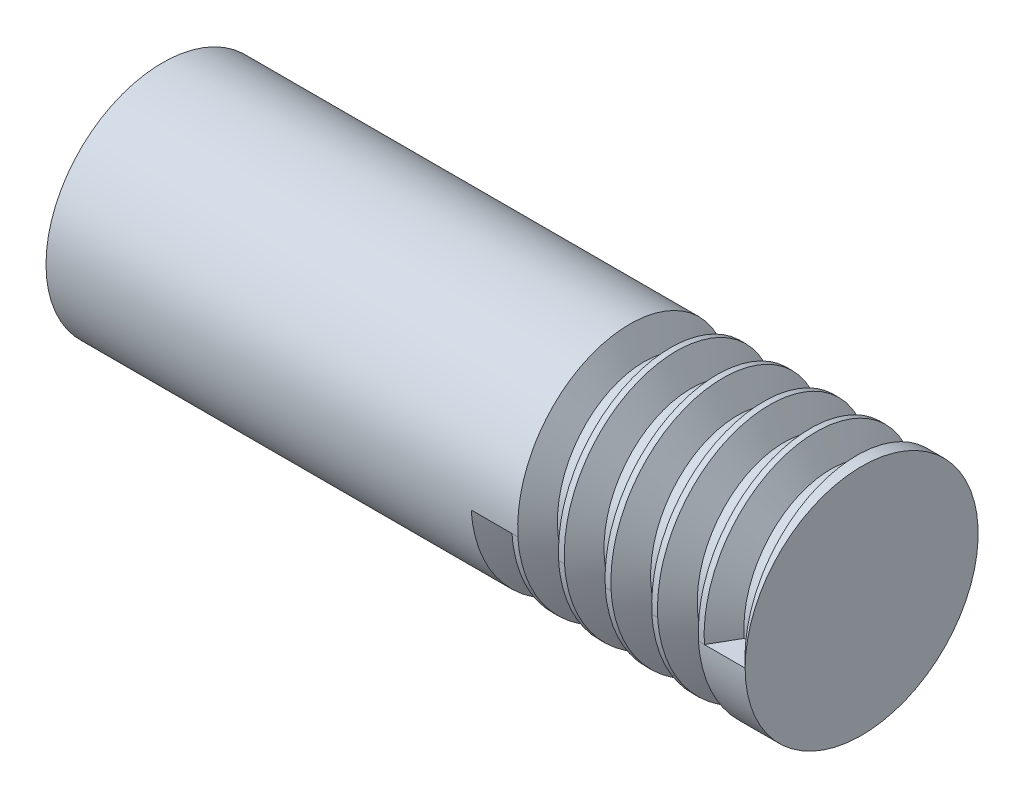
SolidWorks part; units mm, degrees
ref_plane "Front Plane" through (0, 0, 0) normal (0, 0, 1) x (1, 0, 0)
ref_plane "Top Plane" through (0, 0, 0) normal (0, 1, 0) x (1, 0, 0)
ref_plane "Right Plane" through (0, 0, 0) normal (1, 0, 0) x (0, 0, -1)
sketch "Sketch1" plane through (0, 0, 0) normal (1, 0, 0) x (0, 0, -1)
  circle A0 centre (0, 0) radius 5
extrude "Boss-Extrude1" add sketch "Sketch1" along normal blind 30
thread "Thread1" pitch 2 method cut profile "Thread Profile1" start angle 0, offset 0, length 10, pitch 2, diameter 10
ref_plane "Plane1" through (30, 0, 5) normal (0, -1, 0) x (0, 0, 1)
sketch "Thread Profile1" plane through (30, 0, 5) normal (0, -1, 0) x (0, 0, 1)
  line L0 (0, 0) -> (0, 2) construction
  line L11 (0, 0) -> (0, 1.75)
  line L12 (0, 1.75) -> (-1.0825, 1.125)
  line L13 (-1.0825, 1.125) -> (-1.0825, 0.625)
  line L15 (-1.0825, 0.625) -> (0, 0)
  line L17 (-1.0825, 0.875) -> (0, 0.875) construction
  point P2 (0, 0)
  dimension "Pitch" = 2
  dimension "Profile_Angle" = 60
  dimension "Profile_Land" = 0.5
  dimension "Profile_Height" = 1.0825
